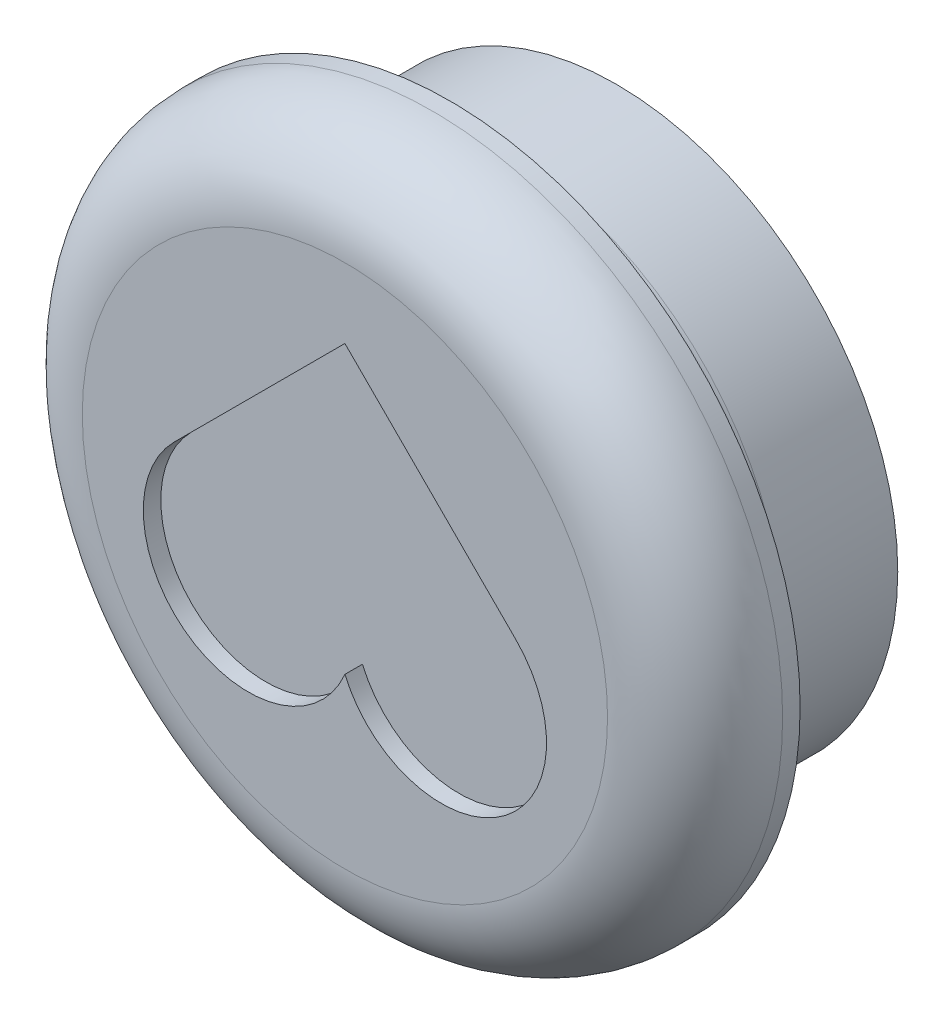
SolidWorks part; units mm, degrees
material "PLA"
ref_plane "前视基准面" through (0, 0, 0) normal (0, 0, 1) x (1, 0, 0)
ref_plane "上视基准面" through (0, 0, 0) normal (0, 1, 0) x (1, 0, 0)
ref_plane "右视基准面" through (0, 0, 0) normal (1, 0, 0) x (0, 0, -1)
sketch "草图1" plane through (0, 0, 0) normal (0, 0, 1) x (1, 0, 0)
  circle A0 centre (0, 0) radius 12.575
  circle A1 centre (0, 0) radius 9.25 construction
  circle A2 centre (0, 0) radius 16.075
  dimension "D1" = 18.5
  dimension "D2" = 25.15
  dimension "D3" = 3.5
extrude "凸台-拉伸1" add sketch "草图1" along normal blind 7.5
sketch "草图2" plane through (0, 0, 7.5) normal (0, 0, 1) x (1, 0, 0)
  circle A0 centre (0, 0) radius 16.075 construction
  circle A1 centre (0, 0) radius 16.075
extrude "凸台-拉伸2" add sketch "草图2" along normal blind 2
sketch "草图3" plane through (0, 0, 9.5) normal (0, 0, 1) x (1, 0, 0)
  circle A0 centre (0, 0) radius 20
  dimension "D1" = 40
extrude "凸台-拉伸3" add sketch "草图3" along normal blind 6
fillet "圆角1" radius 5 1 edges at (20, 0, 15.5)
sketch "草图4" plane through (0, 0, 15.5) normal (0, 0, 1) x (1, 0, 0)
  line L0 (9.7574, 1.2426) -> (0, 11)
  line L1 (0, 11) -> (-9.7574, 1.2426)
  line L2 (0, 0) -> (0, 6.4429) construction
  arc A0 (0, -5.3639) -> (9.7574, 1.2426) centre (5.5147, -3) ccw
  arc A1 (-9.7574, 1.2426) -> (0, -5.3639) centre (-5.5147, -3) ccw
  dimension "D1" = 12
  dimension "D2" = 11
  dimension "D3" = 3
extrude "切除-拉伸1" cut sketch "草图4" against normal blind 1
sketch "草图6" plane through (0, 0, 0) normal (0, 1, 0) x (1, 0, 0)
  line L0 (0, 0) -> (0, -12.1632) construction
  line L1 (10.75, -5) -> (11.05, 0)
  line L2 (16.075, 0) -> (-16.075, 0) construction
  line L3 (11.05, 0) -> (0, 0) construction
  line L4 (0, 0) -> (0, -5) construction
  line L5 (0, -5) -> (10.75, -5) construction
  line L6 (10.75, -5) -> (10.6, -7.5)
  line L7 (10.6, -7.5) -> (0, -7.5) construction
  line L8 (0, -7.5) -> (0, -5) construction
  line L9 (11.05, 0) -> (14, 0)
  line L10 (14, 0) -> (14, -7.5)
  line L11 (14, -7.5) -> (10.6, -7.5)
  point P8 (5.525, 0)
  dimension "D1" = 11.05
  dimension "D2" = 10.75
  dimension "D3" = 5
  dimension "D4" = 7.5
  dimension "D5" = 14
extrude "凸台-拉伸4" add sketch "草图6" along normal blind 7 and the other way blind 7
mirror "镜向1" about plane through (0, 0, 0) normal (1, 0, 0) of "凸台-拉伸4"
sketch "草图5" plane through (0, 0, 7.5) normal (0, 0, -1) x (-1, 0, 0)
  line L0 (7.7677, 9.889) -> (0, 2.1213)
  line L1 (7.46, 7.46) -> (-7.46, -7.46) construction
  line L2 (0, 0) -> (5.7007, 0) construction
  line L3 (-7.7677, -9.889) -> (0, -2.1213)
  line L4 (-7.46, 7.46) -> (7.46, -7.46) construction
  line L5 (-7.7677, 9.889) -> (0, 2.1213)
  line L6 (-9.889, 7.7677) -> (-2.1213, 0)
  line L7 (0, -2.1213) -> (7.7677, -9.889)
  line L8 (2.1213, 0) -> (9.889, 7.7677)
  line L9 (2.1213, 0) -> (9.889, -7.7677)
  line L10 (-2.1213, 0) -> (-9.889, -7.7677)
  line L11 (-10.6, 6.7654) -> (-10.6, -6.7654) construction
  line L12 (-10.6, 6.7654) -> (-10.6, -6.7654)
  line L13 (10.6, 6.7654) -> (10.6, -6.7654) construction
  line L14 (10.6, 6.7654) -> (10.6, -6.7654)
  arc A0 (-9.889, 7.7677) -> (-10.6, 6.7654) centre (0, 0) ccw
  circle A2 centre (0, 0) radius 12.575 construction
  arc A3 (7.7677, 9.889) -> (-7.7677, 9.889) centre (0, 0) ccw
  arc A4 (9.889, -7.7677) -> (10.6, -6.7654) centre (0, 0) ccw
  arc A5 (-7.7677, -9.889) -> (7.7677, -9.889) centre (0, 0) ccw
  arc A6 (-10.6, -6.7654) -> (-9.889, -7.7677) centre (0, 0) ccw
  arc A7 (10.6, 6.7654) -> (9.889, 7.7677) centre (0, 0) ccw
  dimension "D1" = 0
  dimension "D3" = 3
  dimension "D2" = 45
extrude "切除-拉伸2" cut sketch "草图5" against normal blind 4.5
fillet "圆角2" radius 3 1 edges at (16.075, 0, 9.5)
fillet "圆角3" radius 10 2 edges at (10.6, 0, 7.5) (-10.6, 0, 7.5)
fillet "圆角4" radius 1 12 edges at (0, -2.1213, 9.75) (-7.7677, -9.889, 9.75) (-9.889, -7.7677, 9.75) (-2.1213, 0, 9.75) (-9.889, 7.7677, 9.75) (-7.7677, 9.889, 9.75) (0, 2.1213, 9.75) (2.1213, 0, 9.75) (7.7677, 9.889, 9.75) (9.889, 7.7677, 9.75) (9.889, -7.7677, 9.75) (7.7677, -9.889, 9.75)
